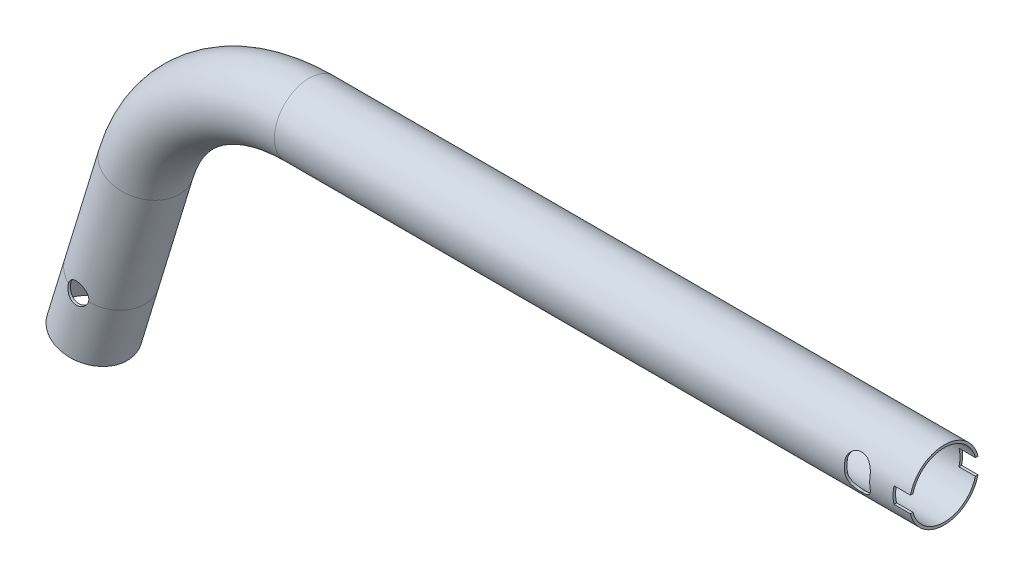
SolidWorks part; units mm, degrees
ref_plane "Front Plane" through (0, 0, 0) normal (0, 0, 1) x (1, 0, 0)
ref_plane "Top Plane" through (0, 0, 0) normal (0, 1, 0) x (1, 0, 0)
ref_plane "Right Plane" through (0, 0, 0) normal (1, 0, 0) x (0, 0, -1)
sketch "Sketch1" plane through (0, 0, 0) normal (0, 0, 1) x (1, 0, 0)
  line L0 (-92.2396, 0) -> (92.2396, 0)
  line L1 (-143.88, -38.2119) -> (-154.7604, -73.8)
  line L2 (92.2396, 0) -> (108.8396, 0)
  line L3 (-154.7604, -73.8) -> (-160.3247, -92)
  arc A0 (-92.2396, 0) -> (-143.88, -38.2119) centre (-92.2396, -54) ccw
  point P4 (0, 0)
  point P10 (-154.7604, -73.8)
  dimension "D2" = 54
  dimension "D1" = 73
  dimension "D3" = 73.8
  dimension "D4" = 247
  dimension "D5" = 92
  dimension "D6" = 73
  dimension "D7" = 16.6
ref_plane "Plane1" through (92.2396, 0, 0) normal (1, 0, 0) x (0, 0, -1)
sketch "Sketch3" plane through (92.2396, 0, 0) normal (1, 0, 0) x (0, 0, -1)
  circle A0 centre (0, 0) radius 11
  circle A1 centre (0, 0) radius 10.2
  dimension "D1" = 0.8
sweep "Sweep2" add profiles "Sketch3" path "Sketch1"
ref_axis "Axis1" through (108.8396, 0, 0) along (-1, 0, 0)
ref_axis "Axis2" through (-142.0816, -32.3296, 0) along (-0.2924, -0.9563, 0)
sketch "Sketch4" plane through (0, 0, 0) normal (0, 0, 1) x (1, 0, 0)
  line L0 (-165.2798, -70.5839) -> (-144.2411, -77.0161) construction
  line L1 (92.2396, -101.4635) -> (92.2396, 101.4635) construction
  line L2 (108.8396, 0) -> (92.2396, 0) construction
  line L3 (108.8396, -11) -> (108.8396, 11) construction
  line L4 (108.8396, 0) -> (-92.2396, 0) construction
  line L5 (108.8396, 2.5555) -> (108.8396, -2.5555)
  line L6 (91.9896, -5.5) -> (92.4896, -5.5)
  line L7 (88.2396, -1.75) -> (88.2396, 1.75)
  line L8 (91.9896, 5.5) -> (92.4896, 5.5)
  line L9 (96.2396, -1.75) -> (96.2396, 1.75)
  line L10 (88.2396, -5.5) -> (96.2396, 5.5) construction
  line L11 (88.2396, 5.5) -> (96.2396, -5.5) construction
  line L12 (105.6396, -2.5555) -> (108.8396, -2.5555)
  line L13 (103.6396, -0.5555) -> (103.6396, 0.5555)
  line L14 (105.6396, 2.5555) -> (108.8396, 2.5555)
  line L16 (103.6396, -2.5555) -> (108.8396, 0) construction
  line L17 (103.6396, 2.5555) -> (108.8396, 0) construction
  line L18 (105.6396, 2.5555) -> (103.6396, 2.5555)
  line L19 (103.6396, 2.5555) -> (103.6396, 0.5555)
  line L20 (103.6396, -0.5555) -> (103.6396, -2.5555)
  line L21 (103.6396, -2.5555) -> (105.6396, -2.5555)
  circle A0 centre (-154.7604, -73.8) radius 3.3
  arc A1 (91.9896, -5.5) -> (88.2396, -1.75) centre (91.9896, -1.75) cw
  arc A2 (96.2396, -1.75) -> (92.4896, -5.5) centre (92.4896, -1.75) cw
  arc A3 (92.4896, 5.5) -> (96.2396, 1.75) centre (92.4896, 1.75) cw
  arc A4 (91.9896, 5.5) -> (88.2396, 1.75) centre (91.9896, 1.75) ccw
  dimension "D1" = 16.6
  dimension "D4" = 3.75
  dimension "D2" = 8
  dimension "D3" = 11
extrude "Cut-Extrude1" cut sketch "Sketch4" along normal up to next
sketch "Sketch5" plane through (0, 0, 0) normal (0, 0, 1) x (1, 0, 0)
  line L0 (-164.5147, -70.8178) -> (-145.0061, -76.7822) construction
  circle A0 centre (-154.7604, -73.8) radius 3.3
extrude "Cut-Extrude2" cut sketch "Sketch5" against normal through all
sketch "Sketch6" plane through (0, 0, 0) normal (0, 0, 1) x (1, 0, 0)
  line L0 (108.8396, -2.5555) -> (108.8396, 2.5555)
  line L1 (108.8396, 2.5555) -> (103.6396, 2.5555)
  line L2 (103.6396, 2.5555) -> (103.6396, -2.5555)
  line L3 (103.6396, -2.5555) -> (108.8396, -2.5555)
extrude "Cut-Extrude3" cut sketch "Sketch6" against normal through all
